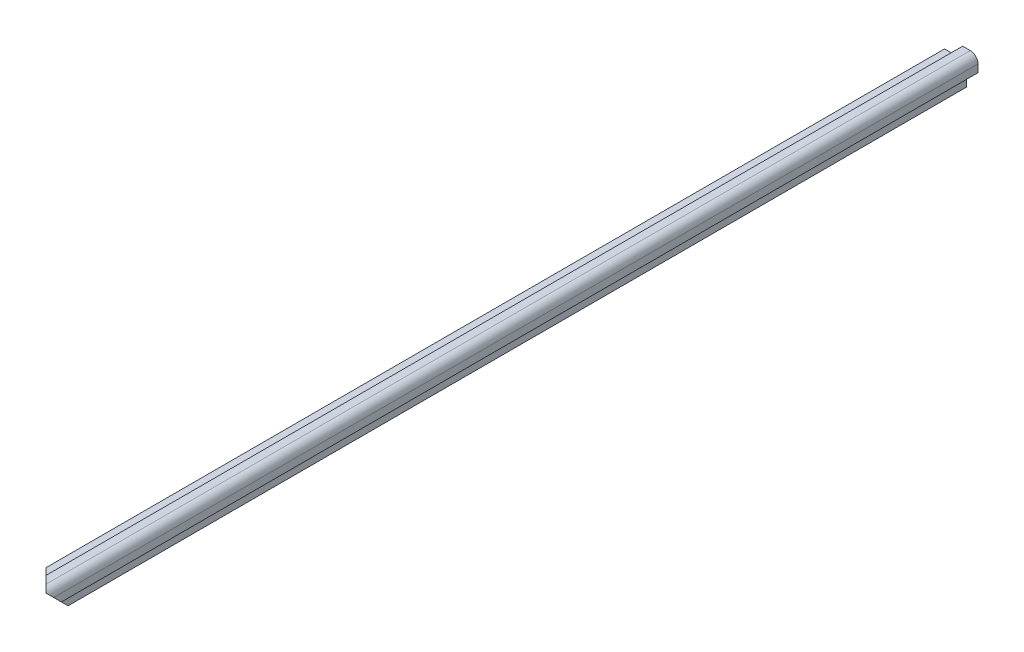
SolidWorks part; units mm, degrees
ref_plane "Front Plane" through (0, 0, 0) normal (0, 0, 1) x (1, 0, 0)
ref_plane "Top Plane" through (0, 0, 0) normal (0, 1, 0) x (1, 0, 0)
ref_plane "Right Plane" through (0, 0, 0) normal (1, 0, 0) x (0, 0, -1)
ref_axis "Axis1" through (0, 0, -88.99) along (0, 0, 1)
sketch "Sketch16" plane through (0, 0, 0) normal (0, 1, 0) x (1, 0, 0)
  line L0 (0, -127) -> (0, 127) construction
  point P2 (0, 0)
  dimension "D1" = 254
sketch "Sketch2" plane through (0, 0, 0) normal (0, 0, 1) x (1, 0, 0)
  line L0 (-7.3025, -1.5) -> (-2.54, -1.5) construction
  line L1 (-7.3025, -1.5) -> (-7.3025, 1.5) construction
  line L2 (-2.54, -1.5) -> (-2.54, 1.5) construction
  line L3 (-7.3025, 1.5) -> (-2.54, 1.5) construction
  line L4 (-2.54, 0) -> (0, 0) construction
  line L5 (0, 0) -> (0, -2.54) construction
  line L6 (-1.5, -2.54) -> (1.5, -2.54) construction
  line L7 (-1.5, -2.54) -> (-1.5, -7.3025) construction
  line L8 (1.5, -2.54) -> (1.5, -7.3025) construction
  line L9 (-1.5, -7.3025) -> (1.5, -7.3025) construction
  point P7 (0, -2.54)
  point P16 (1.5, 1.5)
  dimension "D1" = 3
  dimension "D2" = 4.7625
  dimension "D3" = 2.54
  dimension "D4" = 90
ref_plane "Plane1" through (0, 0, 0) normal (-1, 0, 0) x (0, -1, 0)
sketch "Sketch7" plane through (0, 0, 0) normal (0, 0, 1) x (1, 0, 0)
  line L0 (-7.3025, -1.5) -> (-2.54, -1.5)
  line L1 (-7.3025, -1.5) -> (-7.3025, -3.6212)
  line L2 (-2.54, -1.5) -> (-2.54, -3.6212)
  line L3 (-7.3025, -3.6212) -> (-2.54, -3.6212)
  dimension "D1" = 2.1212
extrude "Boss-Extrude2" add sketch "Sketch7" along normal mid plane 260.35 separate body
sketch "Sketch8" plane through (0, 0, 0) normal (0, 0, 1) x (1, 0, 0)
  line L0 (-1.5, -2.54) -> (-1.5, -7.3025)
  line L1 (-1.5, -2.54) -> (-3.6212, -2.54)
  line L2 (-1.5, -7.3025) -> (-3.6212, -7.3025)
  line L3 (-3.6212, -2.54) -> (-3.6212, -7.3025)
  line L4 (-2.54, -3.6212) -> (-2.54, -1.5) construction
extrude "Boss-Extrude3" add sketch "Sketch8" along normal mid plane 260.35
sketch "Sketch11" plane through (0, 0, 0) normal (0, 0, 1) x (1, 0, 0)
  line L0 (-2.54, 1.5) -> (-2.54, -1.5)
  line L1 (-2.54, -1.5) -> (-7.3025, -1.5)
  line L2 (-7.3025, -1.5) -> (-7.3025, -3.6212)
  line L3 (-7.3025, -3.6212) -> (-5.8663, -3.6212)
  line L4 (-7.3025, -3.6212) -> (-3.6212, -3.6212) construction
  line L5 (-5.8663, -3.6212) -> (-3.6212, -5.8663)
  line L6 (-3.6212, -3.6212) -> (-3.6212, -7.3025) construction
  line L7 (-3.6212, -5.8663) -> (-3.6212, -7.3025)
  line L8 (-3.6212, -7.3025) -> (-1.5, -7.3025)
  line L9 (-1.5, -7.3025) -> (-1.5, -2.54)
  line L10 (-1.5, -2.54) -> (1.5, -2.54)
  line L13 (-2.54, 1.5) -> (-2.54, -2.54) construction
  line L14 (-2.54, -2.54) -> (1.5, -2.54) construction
  line L15 (1.5, -0.52) -> (1.5, -2.54)
  line L17 (-2.54, 1.5) -> (-0.52, 1.5)
  arc A1 (-0.52, 1.5) -> (1.5, -0.52) centre (-0.52, -0.52) cw
  point P25 (0, 0)
  dimension "D1" = 3.175
extrude "Boss-Extrude4" add sketch "Sketch11" along normal mid plane 260.35
ref_plane "Midplane" through (0, 0, 0) normal (-0.7071, 0.7071, 0) x (0.7071, 0.7071, 0)
sketch "Sketch17" plane through (0, 0, 113.7049) normal (-0.5774, -0.5774, -0.5774) x (0.7071, 0, -0.7071)
  line L0 (0, 0) -> (9.3473, -5.3967) construction
  line L1 (-9.3473, -5.3967) -> (0, 0) construction
  line L2 (-47.0981, -27.1921) -> (0, 0) construction
  line L3 (0, 0) -> (0, 10.7933) construction
  line L4 (9.3473, 5.3967) -> (0, 0)
  line L5 (0, 10.7933) -> (-9.3473, 5.3967) construction
  line L6 (-9.3473, 5.3967) -> (-9.3473, -5.3967) construction
  line L7 (-9.3473, -5.3967) -> (0, -10.7933) construction
  line L8 (0, -10.7933) -> (9.3473, -5.3967) construction
  line L9 (9.3473, -5.3967) -> (9.3473, 5.3967) construction
  line L10 (9.3473, 5.3967) -> (0, 10.7933) construction
  line L11 (0, 0) -> (0, -10.7933)
  line L12 (0, -10.7933) -> (-219.9705, 116.2067)
  line L13 (-219.9705, 116.2067) -> (-210.6232, 132.3967)
  line L14 (-210.6232, 132.3967) -> (9.3473, 5.3967)
  circle A0 centre (0, 0) radius 9.3473 construction
  point P4 (-45.165, 15.2827)
  dimension "D1" = 254
extrude "Cut-Extrude1" cut sketch "Sketch17" against normal through all both and the other way through all
equation "\"plate_thickness\"= 3mm"
equation "\"D1@Sketch2\"=\"plate_thickness\""
equation "\"joiner_lip_width\"= .1875"
equation "\"D2@Sketch2\"=\"joiner_lip_width\""
equation "\"face_gap\"=0.1"
equation "\"D3@Sketch2\"=\"face_gap\""
equation "\"inside_angle\"= 90"
equation "\"joiner_thickness\"= 0.0835128"
equation "\"edge_length\"= 10"
equation "\"Face1_TopLip\"= \"angle\" * 2"
equation "\"Face1_BottomLip\"= \"angle\" * 2"
equation "\"Face2_TopLip\"= 45deg"
equation "\"Face2_BottomLip\"= 45deg"
equation "\"D1@Sketch7\"=\"joiner_thickness\""
equation "\"D1@Boss-Extrude2\"=\"Extrude_to\""
equation "\"D1@Boss-Extrude3\"=\"Extrude_to\""
equation "\"D1@Boss-Extrude4\"=\"Extrude_to\""
equation "\"D4@Sketch2\"=\"inside_angle\""
equation "\"Extrude_to\"= \"edge_length\" + .25"
equation "\"D1@Sketch16\"=\"edge_length\""
equation "\"angle\"= atn ( 0.1 / ( ( 3.7085 - 3.0793 ) / 2 ) )"
equation "\"D2@Sketch5\"=\"Face2_TopLip\"/2"
equation "\"D1@Sketch5\"=\"Face2_BottomLip\"/2"
equation "\"D2@Sketch4\"=\"Face1_TopLip\"/2"
equation "\"D1@Sketch4\"=\"Face1_BottomLip\"/2"
equation "\"D1\" = \"edge_length\""
equation "\"D2@Sketch12\"=\"Face1_TopLip\"/2"
equation "\"D1@Sketch12\"=\"Face1_BottomLip\"/2"
